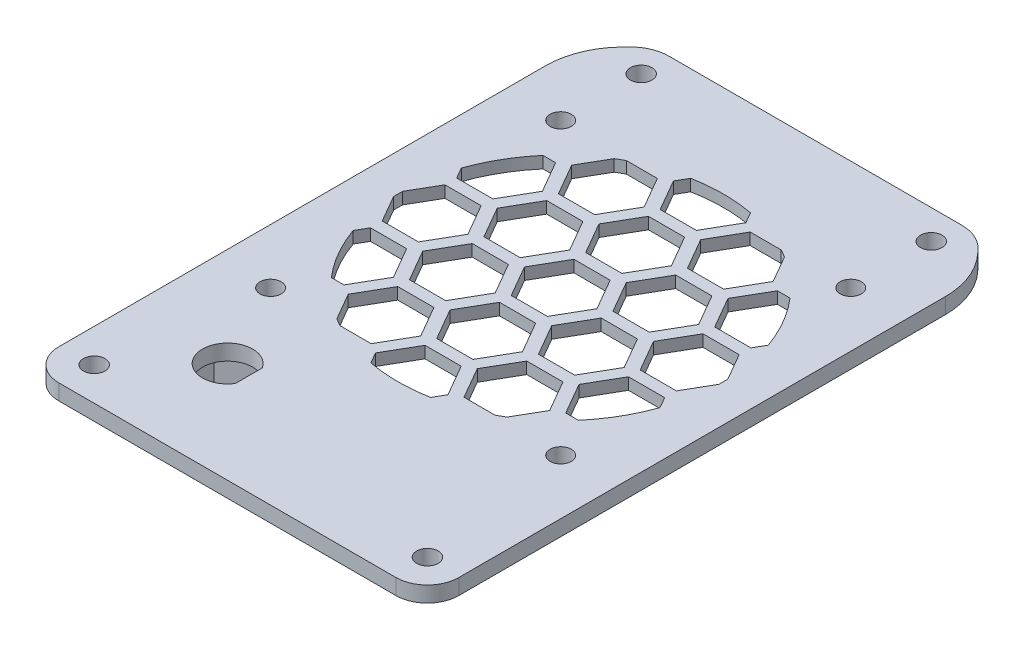
SolidWorks part; units mm, degrees
ref_plane "Front Plane" through (0, 0, 0) normal (0, 0, 1) x (1, 0, 0)
ref_plane "Top Plane" through (0, 0, 0) normal (0, 1, 0) x (1, 0, 0)
ref_plane "Right Plane" through (0, 0, 0) normal (1, 0, 0) x (0, 0, -1)
sketch "Sketch1" plane through (0, -8.5812, 0) normal (0, 1, 0) x (1, 0, 0)
  line L0 (-23.1823, 1.3362) -> (-42.1823, 1.3362)
  line L16 (-54.1823, -73.6638) -> (-11.1823, -73.6638)
  line L17 (-7.1823, -69.6638) -> (-7.1823, -7.6054)
  line L18 (-9.8717, -0.7822) -> (-11.849, 1.3362)
  line L19 (-11.849, 1.3362) -> (-23.1823, 1.3362)
  line L20 (-23.1823, 1.3362) -> (-23.1823, -1.1769)
  line L21 (-23.1823, -1.1769) -> (-10.589, -9.0704)
  line L22 (-9.1823, -11.6123) -> (-9.1823, -59.6638)
  line L23 (-9.1823, -59.6638) -> (-21.1823, -71.6638)
  line L24 (-21.1823, -71.6638) -> (-44.1823, -71.6638)
  line L25 (-44.1823, -71.6638) -> (-56.1823, -59.6638)
  line L26 (-56.1823, -59.6638) -> (-56.1823, -11.6123)
  line L27 (-54.7756, -9.0704) -> (-42.1823, -1.1769)
  line L28 (-42.1823, -1.1769) -> (-42.1823, 1.3362)
  line L29 (-42.1823, 1.3362) -> (-53.5156, 1.3362)
  line L30 (-53.5156, 1.3362) -> (-55.4928, -0.7822)
  line L31 (-58.1823, -7.6054) -> (-58.1823, -69.6638)
  line L32 (-54.1823, -73.6638) -> (-11.1823, -73.6638)
  line L33 (-7.1823, -69.6638) -> (-7.1823, -7.6054)
  line L34 (-9.8717, -0.7822) -> (-11.849, 1.3362)
  line L35 (-11.849, 1.3362) -> (-23.1823, 1.3362)
  line L36 (-23.1823, 1.3362) -> (-23.1823, -1.1769)
  line L37 (-23.1823, -1.1769) -> (-10.589, -9.0704)
  line L38 (-9.1823, -11.6123) -> (-9.1823, -59.6638)
  line L39 (-9.1823, -59.6638) -> (-21.1823, -71.6638)
  line L40 (-21.1823, -71.6638) -> (-44.1823, -71.6638)
  line L41 (-44.1823, -71.6638) -> (-56.1823, -59.6638)
  line L42 (-56.1823, -59.6638) -> (-56.1823, -11.6123)
  line L43 (-54.7756, -9.0704) -> (-42.1823, -1.1769)
  line L44 (-42.1823, -1.1769) -> (-42.1823, 1.3362)
  line L45 (-42.1823, 1.3362) -> (-53.5156, 1.3362)
  line L46 (-53.5156, 1.3362) -> (-55.4928, -0.7822)
  line L47 (-58.1823, -7.6054) -> (-58.1823, -69.6638)
  circle A0 centre (-14.1823, -2.3941) radius 1.375
  circle A1 centre (-51.1823, -2.3941) radius 1.375
  circle A2 centre (-11.4323, -69.4138) radius 1.375
  circle A3 centre (-53.9323, -69.4138) radius 1.375
  arc A6 (-11.1823, -73.6638) -> (-7.1823, -69.6638) centre (-11.1823, -69.6638) ccw
  arc A7 (-7.1823, -7.6054) -> (-9.8717, -0.7822) centre (-17.1823, -7.6054) ccw
  arc A8 (-9.1823, -11.6123) -> (-10.589, -9.0704) centre (-12.1823, -11.6123) ccw
  arc A9 (-54.7756, -9.0704) -> (-56.1823, -11.6123) centre (-53.1823, -11.6123) ccw
  arc A10 (-55.4928, -0.7822) -> (-58.1823, -7.6054) centre (-48.1823, -7.6054) ccw
  arc A11 (-58.1823, -69.6638) -> (-54.1823, -73.6638) centre (-54.1823, -69.6638) ccw
  arc A12 (-11.1823, -73.6638) -> (-7.1823, -69.6638) centre (-11.1823, -69.6638) ccw
  arc A13 (-7.1823, -7.6054) -> (-9.8717, -0.7822) centre (-17.1823, -7.6054) ccw
  arc A14 (-9.1823, -11.6123) -> (-10.589, -9.0704) centre (-12.1823, -11.6123) ccw
  arc A15 (-54.7756, -9.0704) -> (-56.1823, -11.6123) centre (-53.1823, -11.6123) ccw
  arc A16 (-55.4928, -0.7822) -> (-58.1823, -7.6054) centre (-48.1823, -7.6054) ccw
  arc A17 (-58.1823, -69.6638) -> (-54.1823, -73.6638) centre (-54.1823, -69.6638) ccw
  circle M24 centre (-51.1823, -2.3941) radius 2.3
  circle M25 centre (-11.4323, -69.4138) radius 2.3
  circle M26 centre (-53.9323, -69.4138) radius 2.3
  circle M27 centre (-14.1823, -2.3941) radius 2.3
  line M28 (-54.1823, -73.6638) -> (-11.1823, -73.6638)
  arc M29 (-11.1823, -73.6638) -> (-7.1823, -69.6638) centre (-11.1823, -69.6638) ccw
  line M30 (-7.1823, -69.6638) -> (-7.1823, -7.6054)
  arc M31 (-7.1823, -7.6054) -> (-9.8717, -0.7822) centre (-17.1823, -7.6054) ccw
  line M32 (-9.8717, -0.7822) -> (-11.849, 1.3362)
  line M33 (-11.849, 1.3362) -> (-23.1823, 1.3362)
  line M34 (-23.1823, 1.3362) -> (-23.1823, -1.1769)
  line M35 (-23.1823, -1.1769) -> (-10.589, -9.0704)
  arc M36 (-10.589, -9.0704) -> (-9.1823, -11.6123) centre (-12.1823, -11.6123) cw
  line M37 (-9.1823, -11.6123) -> (-9.1823, -59.6638)
  line M38 (-9.1823, -59.6638) -> (-21.1823, -71.6638)
  line M39 (-21.1823, -71.6638) -> (-44.1823, -71.6638)
  line M40 (-44.1823, -71.6638) -> (-56.1823, -59.6638)
  line M41 (-56.1823, -59.6638) -> (-56.1823, -11.6123)
  arc M42 (-56.1823, -11.6123) -> (-54.7756, -9.0704) centre (-53.1823, -11.6123) cw
  line M43 (-54.7756, -9.0704) -> (-42.1823, -1.1769)
  line M44 (-42.1823, -1.1769) -> (-42.1823, 1.3362)
  line M45 (-42.1823, 1.3362) -> (-53.5156, 1.3362)
  line M46 (-53.5156, 1.3362) -> (-55.4928, -0.7822)
  arc M47 (-55.4928, -0.7822) -> (-58.1823, -7.6054) centre (-48.1823, -7.6054) ccw
  line M48 (-58.1823, -7.6054) -> (-58.1823, -69.6638)
  arc M49 (-58.1823, -69.6638) -> (-54.1823, -73.6638) centre (-54.1823, -69.6638) ccw
  dimension "D2" = 2.75
  dimension "D3" = 2.75
  dimension "D4" = 2.75
  dimension "D5" = 2.75
  dimension "D1" = 0
extrude "Boss-Extrude1" add sketch "Sketch1" along normal blind 2 contours M49 M28 M29 M30 M31 M32 M33 M34 M35 M36 M37 M38 M39 M40 M41 M42 M43 M44 M45 M46 M47 M48 M25 M27 M26 M24 | L0 M34 M44 M43 M42 M41 M40 M39 M38 M37 M36 M35 | A0 M27 | A1 M24 | A3 M26 | A2 M25 region at (-32.6823, -8.5812, 35.6933) region at (-17.5156, -8.5812, -0.4292) region at (-53.4172, -8.5812, 2.3941) region at (-13.6672, -8.5812, 69.4138) region at (-56.1672, -8.5812, 69.4138) region at (-16.4172, -8.5812, 2.3941)
fillet "Fillet1" radius 5 2 edges at (-11.849, -7.5812, -1.3362) (-53.5156, -7.5812, -1.3362)
sketch "Sketch2" plane through (0, -6.5812, 0) normal (0, 1, 0) x (1, 0, 0)
  circle A1 centre (-32.6823, -31.1638) radius 20.75
  circle A2 centre (-32.6823, -31.1638) radius 20.75
  dimension "D1" = 0
extrude "Cut-Extrude1" cut sketch "Sketch2" against normal through all
sketch "Sketch3" plane through (0, -8.5812, 0) normal (0, -1, 0) x (1, 0, 0)
  circle A2 centre (-32.6823, 31.1638) radius 21.75
  circle A3 centre (-32.6823, 31.1638) radius 21.75
  dimension "D1" = 1
extrude "Cut-Extrude2" cut sketch "Sketch3" against normal blind 0.5
sketch "Sketch4" plane through (0, -6.5812, 0) normal (0, 1, 0) x (1, 0, 0)
  line L0 (-49.1368, -12.1638) -> (-40.9095, -16.9138) construction
  line L1 (-38.6001, -12.9138) -> (-43.2189, -12.9138)
  line L2 (-43.2189, -12.9138) -> (-45.5283, -16.9138)
  line L3 (-45.5283, -16.9138) -> (-43.2189, -20.9138)
  line L4 (-43.2189, -20.9138) -> (-38.6001, -20.9138)
  line L5 (-38.6001, -20.9138) -> (-36.2907, -16.9138)
  line L6 (-36.2907, -16.9138) -> (-38.6001, -12.9138)
  line L7 (-44.518, -12.1638) -> (-46.8274, -8.1638)
  line L8 (-46.8274, -8.1638) -> (-51.4462, -8.1638)
  line L9 (-51.4462, -8.1638) -> (-53.7556, -12.1638)
  line L10 (-53.7556, -12.1638) -> (-51.4462, -16.1638)
  line L11 (-51.4462, -16.1638) -> (-46.8274, -16.1638)
  line L12 (-46.8274, -16.1638) -> (-44.518, -12.1638)
  line L13 (-22.1456, -12.9138) -> (-26.7644, -12.9138)
  line L14 (-26.7644, -12.9138) -> (-29.0738, -16.9138)
  line L15 (-29.0738, -16.9138) -> (-26.7644, -20.9138)
  line L16 (-26.7644, -20.9138) -> (-22.1456, -20.9138)
  line L17 (-22.1456, -20.9138) -> (-19.8362, -16.9138)
  line L18 (-19.8362, -16.9138) -> (-22.1456, -12.9138)
  line L19 (-28.0635, -12.1638) -> (-30.3729, -8.1638)
  line L20 (-34.9917, -8.1638) -> (-37.3011, -12.1638)
  line L21 (-37.3011, -12.1638) -> (-34.9917, -16.1638)
  line L22 (-34.9917, -16.1638) -> (-30.3729, -16.1638)
  line L23 (-30.3729, -16.1638) -> (-28.0635, -12.1638)
  line L24 (-32.6823, -12.1638) -> (-24.455, -16.9138) construction
  line L25 (-30.3729, -8.1638) -> (-34.9917, -8.1638)
  line L26 (-5.6912, -12.9138) -> (-10.31, -12.9138)
  line L27 (-10.31, -12.9138) -> (-12.6194, -16.9138)
  line L28 (-12.6194, -16.9138) -> (-10.31, -20.9138)
  line L29 (-10.31, -20.9138) -> (-5.6912, -20.9138)
  line L30 (-5.6912, -20.9138) -> (-3.3818, -16.9138)
  line L31 (-3.3818, -16.9138) -> (-5.6912, -12.9138)
  line L32 (-11.609, -12.1638) -> (-13.9184, -8.1638)
  line L33 (-18.5372, -8.1638) -> (-20.8466, -12.1638)
  line L34 (-20.8466, -12.1638) -> (-18.5372, -16.1638)
  line L35 (-18.5372, -16.1638) -> (-13.9184, -16.1638)
  line L36 (-13.9184, -16.1638) -> (-11.609, -12.1638)
  line L37 (-16.2278, -12.1638) -> (-8.0006, -16.9138) construction
  line L38 (-13.9184, -8.1638) -> (-18.5372, -8.1638)
  line L39 (-22.1456, -22.4138) -> (-26.7644, -22.4138)
  line L40 (-26.7644, -22.4138) -> (-29.0738, -26.4138)
  line L41 (-29.0738, -26.4138) -> (-26.7644, -30.4138)
  line L42 (-26.7644, -30.4138) -> (-22.1456, -30.4138)
  line L43 (-22.1456, -30.4138) -> (-19.8362, -26.4138)
  line L44 (-19.8362, -26.4138) -> (-22.1456, -22.4138)
  line L45 (-28.0635, -21.6638) -> (-30.3729, -17.6638)
  line L46 (-34.9917, -17.6638) -> (-37.3011, -21.6638)
  line L47 (-37.3011, -21.6638) -> (-34.9917, -25.6638)
  line L48 (-34.9917, -25.6638) -> (-30.3729, -25.6638)
  line L49 (-30.3729, -25.6638) -> (-28.0635, -21.6638)
  line L50 (-32.6823, -21.6638) -> (-24.455, -26.4138) construction
  line L51 (-30.3729, -17.6638) -> (-34.9917, -17.6638)
  line L52 (-5.6912, -22.4138) -> (-10.31, -22.4138)
  line L53 (-10.31, -22.4138) -> (-12.6194, -26.4138)
  line L54 (-12.6194, -26.4138) -> (-10.31, -30.4138)
  line L55 (-10.31, -30.4138) -> (-5.6912, -30.4138)
  line L56 (-5.6912, -30.4138) -> (-3.3818, -26.4138)
  line L57 (-3.3818, -26.4138) -> (-5.6912, -22.4138)
  line L58 (-11.609, -21.6638) -> (-13.9184, -17.6638)
  line L59 (-18.5372, -17.6638) -> (-20.8466, -21.6638)
  line L60 (-20.8466, -21.6638) -> (-18.5372, -25.6638)
  line L61 (-18.5372, -25.6638) -> (-13.9184, -25.6638)
  line L62 (-13.9184, -25.6638) -> (-11.609, -21.6638)
  line L63 (-16.2278, -21.6638) -> (-8.0006, -26.4138) construction
  line L64 (-13.9184, -17.6638) -> (-18.5372, -17.6638)
  line L65 (-22.1456, -31.9138) -> (-26.7644, -31.9138)
  line L66 (-26.7644, -31.9138) -> (-29.0738, -35.9138)
  line L67 (-29.0738, -35.9138) -> (-26.7644, -39.9138)
  line L68 (-26.7644, -39.9138) -> (-22.1456, -39.9138)
  line L69 (-22.1456, -39.9138) -> (-19.8362, -35.9138)
  line L70 (-19.8362, -35.9138) -> (-22.1456, -31.9138)
  line L71 (-28.0635, -31.1638) -> (-30.3729, -27.1638)
  line L72 (-34.9917, -27.1638) -> (-37.3011, -31.1638)
  line L73 (-37.3011, -31.1638) -> (-34.9917, -35.1638)
  line L74 (-34.9917, -35.1638) -> (-30.3729, -35.1638)
  line L75 (-30.3729, -35.1638) -> (-28.0635, -31.1638)
  line L76 (-32.6823, -31.1638) -> (-24.455, -35.9138) construction
  line L77 (-30.3729, -27.1638) -> (-34.9917, -27.1638)
  line L78 (-5.6912, -31.9138) -> (-10.31, -31.9138)
  line L79 (-10.31, -31.9138) -> (-12.6194, -35.9138)
  line L80 (-12.6194, -35.9138) -> (-10.31, -39.9138)
  line L81 (-10.31, -39.9138) -> (-5.6912, -39.9138)
  line L82 (-5.6912, -39.9138) -> (-3.3818, -35.9138)
  line L83 (-3.3818, -35.9138) -> (-5.6912, -31.9138)
  line L84 (-11.609, -31.1638) -> (-13.9184, -27.1638)
  line L85 (-18.5372, -27.1638) -> (-20.8466, -31.1638)
  line L86 (-20.8466, -31.1638) -> (-18.5372, -35.1638)
  line L87 (-18.5372, -35.1638) -> (-13.9184, -35.1638)
  line L88 (-13.9184, -35.1638) -> (-11.609, -31.1638)
  line L89 (-16.2278, -31.1638) -> (-8.0006, -35.9138) construction
  line L90 (-13.9184, -27.1638) -> (-18.5372, -27.1638)
  line L91 (-22.1456, -41.4138) -> (-26.7644, -41.4138)
  line L92 (-26.7644, -41.4138) -> (-29.0738, -45.4138)
  line L93 (-29.0738, -45.4138) -> (-26.7644, -49.4138)
  line L94 (-26.7644, -49.4138) -> (-22.1456, -49.4138)
  line L95 (-22.1456, -49.4138) -> (-19.8362, -45.4138)
  line L96 (-19.8362, -45.4138) -> (-22.1456, -41.4138)
  line L97 (-28.0635, -40.6638) -> (-30.3729, -36.6638)
  line L98 (-34.9917, -36.6638) -> (-37.3011, -40.6638)
  line L99 (-37.3011, -40.6638) -> (-34.9917, -44.6638)
  line L100 (-34.9917, -44.6638) -> (-30.3729, -44.6638)
  line L101 (-30.3729, -44.6638) -> (-28.0635, -40.6638)
  line L102 (-32.6823, -40.6638) -> (-24.455, -45.4138) construction
  line L103 (-30.3729, -36.6638) -> (-34.9917, -36.6638)
  line L104 (-5.6912, -41.4138) -> (-10.31, -41.4138)
  line L105 (-10.31, -41.4138) -> (-12.6194, -45.4138)
  line L106 (-12.6194, -45.4138) -> (-10.31, -49.4138)
  line L107 (-10.31, -49.4138) -> (-5.6912, -49.4138)
  line L108 (-5.6912, -49.4138) -> (-3.3818, -45.4138)
  line L109 (-3.3818, -45.4138) -> (-5.6912, -41.4138)
  line L110 (-11.609, -40.6638) -> (-13.9184, -36.6638)
  line L111 (-18.5372, -36.6638) -> (-20.8466, -40.6638)
  line L112 (-20.8466, -40.6638) -> (-18.5372, -44.6638)
  line L113 (-18.5372, -44.6638) -> (-13.9184, -44.6638)
  line L114 (-13.9184, -44.6638) -> (-11.609, -40.6638)
  line L115 (-16.2278, -40.6638) -> (-8.0006, -45.4138) construction
  line L116 (-13.9184, -36.6638) -> (-18.5372, -36.6638)
  line L117 (-22.1456, -50.9138) -> (-26.7644, -50.9138)
  line L118 (-26.7644, -50.9138) -> (-29.0738, -54.9138)
  line L119 (-29.0738, -54.9138) -> (-26.7644, -58.9138)
  line L120 (-26.7644, -58.9138) -> (-22.1456, -58.9138)
  line L121 (-22.1456, -58.9138) -> (-19.8362, -54.9138)
  line L122 (-19.8362, -54.9138) -> (-22.1456, -50.9138)
  line L123 (-28.0635, -50.1638) -> (-30.3729, -46.1638)
  line L124 (-34.9917, -46.1638) -> (-37.3011, -50.1638)
  line L125 (-37.3011, -50.1638) -> (-34.9917, -54.1638)
  line L126 (-34.9917, -54.1638) -> (-30.3729, -54.1638)
  line L127 (-30.3729, -54.1638) -> (-28.0635, -50.1638)
  line L128 (-32.6823, -50.1638) -> (-24.455, -54.9138) construction
  line L129 (-30.3729, -46.1638) -> (-34.9917, -46.1638)
  line L130 (-5.6912, -50.9138) -> (-10.31, -50.9138)
  line L131 (-10.31, -50.9138) -> (-12.6194, -54.9138)
  line L132 (-12.6194, -54.9138) -> (-10.31, -58.9138)
  line L133 (-10.31, -58.9138) -> (-5.6912, -58.9138)
  line L134 (-5.6912, -58.9138) -> (-3.3818, -54.9138)
  line L135 (-3.3818, -54.9138) -> (-5.6912, -50.9138)
  line L136 (-11.609, -50.1638) -> (-13.9184, -46.1638)
  line L137 (-18.5372, -46.1638) -> (-20.8466, -50.1638)
  line L138 (-20.8466, -50.1638) -> (-18.5372, -54.1638)
  line L139 (-18.5372, -54.1638) -> (-13.9184, -54.1638)
  line L140 (-13.9184, -54.1638) -> (-11.609, -50.1638)
  line L141 (-16.2278, -50.1638) -> (-8.0006, -54.9138) construction
  line L142 (-13.9184, -46.1638) -> (-18.5372, -46.1638)
  line L143 (-38.6001, -22.4138) -> (-43.2189, -22.4138)
  line L144 (-43.2189, -22.4138) -> (-45.5283, -26.4138)
  line L145 (-45.5283, -26.4138) -> (-43.2189, -30.4138)
  line L146 (-43.2189, -30.4138) -> (-38.6001, -30.4138)
  line L147 (-38.6001, -30.4138) -> (-36.2907, -26.4138)
  line L148 (-36.2907, -26.4138) -> (-38.6001, -22.4138)
  line L149 (-44.518, -21.6638) -> (-46.8274, -17.6638)
  line L150 (-51.4462, -17.6638) -> (-53.7556, -21.6638)
  line L151 (-53.7556, -21.6638) -> (-51.4462, -25.6638)
  line L152 (-51.4462, -25.6638) -> (-46.8274, -25.6638)
  line L153 (-46.8274, -25.6638) -> (-44.518, -21.6638)
  line L154 (-49.1368, -21.6638) -> (-40.9095, -26.4138) construction
  line L155 (-46.8274, -17.6638) -> (-51.4462, -17.6638)
  line L156 (-38.6001, -31.9138) -> (-43.2189, -31.9138)
  line L157 (-43.2189, -31.9138) -> (-45.5283, -35.9138)
  line L158 (-45.5283, -35.9138) -> (-43.2189, -39.9138)
  line L159 (-43.2189, -39.9138) -> (-38.6001, -39.9138)
  line L160 (-38.6001, -39.9138) -> (-36.2907, -35.9138)
  line L161 (-36.2907, -35.9138) -> (-38.6001, -31.9138)
  line L162 (-44.518, -31.1638) -> (-46.8274, -27.1638)
  line L163 (-51.4462, -27.1638) -> (-53.7556, -31.1638)
  line L164 (-53.7556, -31.1638) -> (-51.4462, -35.1638)
  line L165 (-51.4462, -35.1638) -> (-46.8274, -35.1638)
  line L166 (-46.8274, -35.1638) -> (-44.518, -31.1638)
  line L167 (-49.1368, -31.1638) -> (-40.9095, -35.9138) construction
  line L168 (-46.8274, -27.1638) -> (-51.4462, -27.1638)
  line L169 (-38.6001, -41.4138) -> (-43.2189, -41.4138)
  line L170 (-43.2189, -41.4138) -> (-45.5283, -45.4138)
  line L171 (-45.5283, -45.4138) -> (-43.2189, -49.4138)
  line L172 (-43.2189, -49.4138) -> (-38.6001, -49.4138)
  line L173 (-38.6001, -49.4138) -> (-36.2907, -45.4138)
  line L174 (-36.2907, -45.4138) -> (-38.6001, -41.4138)
  line L175 (-44.518, -40.6638) -> (-46.8274, -36.6638)
  line L176 (-51.4462, -36.6638) -> (-53.7556, -40.6638)
  line L177 (-53.7556, -40.6638) -> (-51.4462, -44.6638)
  line L178 (-51.4462, -44.6638) -> (-46.8274, -44.6638)
  line L179 (-46.8274, -44.6638) -> (-44.518, -40.6638)
  line L180 (-49.1368, -40.6638) -> (-40.9095, -45.4138) construction
  line L181 (-46.8274, -36.6638) -> (-51.4462, -36.6638)
  line L182 (-38.6001, -50.9138) -> (-43.2189, -50.9138)
  line L183 (-43.2189, -50.9138) -> (-45.5283, -54.9138)
  line L184 (-45.5283, -54.9138) -> (-43.2189, -58.9138)
  line L185 (-43.2189, -58.9138) -> (-38.6001, -58.9138)
  line L186 (-38.6001, -58.9138) -> (-36.2907, -54.9138)
  line L187 (-36.2907, -54.9138) -> (-38.6001, -50.9138)
  line L188 (-44.518, -50.1638) -> (-46.8274, -46.1638)
  line L189 (-51.4462, -46.1638) -> (-53.7556, -50.1638)
  line L190 (-53.7556, -50.1638) -> (-51.4462, -54.1638)
  line L191 (-51.4462, -54.1638) -> (-46.8274, -54.1638)
  line L192 (-46.8274, -54.1638) -> (-44.518, -50.1638)
  line L193 (-49.1368, -50.1638) -> (-40.9095, -54.9138) construction
  line L194 (-46.8274, -46.1638) -> (-51.4462, -46.1638)
  circle A0 centre (-40.9095, -16.9138) radius 4 construction
  circle A1 centre (-49.1368, -12.1638) radius 4 construction
  circle A2 centre (-24.455, -16.9138) radius 4 construction
  circle A3 centre (-32.6823, -12.1638) radius 4 construction
  circle A4 centre (-8.0006, -16.9138) radius 4 construction
  circle A5 centre (-16.2278, -12.1638) radius 4 construction
  circle A6 centre (-24.455, -26.4138) radius 4 construction
  circle A7 centre (-32.6823, -21.6638) radius 4 construction
  circle A8 centre (-8.0006, -26.4138) radius 4 construction
  circle A9 centre (-16.2278, -21.6638) radius 4 construction
  circle A10 centre (-24.455, -35.9138) radius 4 construction
  circle A11 centre (-32.6823, -31.1638) radius 4 construction
  circle A12 centre (-8.0006, -35.9138) radius 4 construction
  circle A13 centre (-16.2278, -31.1638) radius 4 construction
  circle A14 centre (-24.455, -45.4138) radius 4 construction
  circle A15 centre (-32.6823, -40.6638) radius 4 construction
  circle A16 centre (-8.0006, -45.4138) radius 4 construction
  circle A17 centre (-16.2278, -40.6638) radius 4 construction
  circle A18 centre (-24.455, -54.9138) radius 4 construction
  circle A19 centre (-32.6823, -50.1638) radius 4 construction
  circle A20 centre (-8.0006, -54.9138) radius 4 construction
  circle A21 centre (-16.2278, -50.1638) radius 4 construction
  circle A22 centre (-40.9095, -26.4138) radius 4 construction
  circle A23 centre (-49.1368, -21.6638) radius 4 construction
  circle A24 centre (-40.9095, -35.9138) radius 4 construction
  circle A25 centre (-49.1368, -31.1638) radius 4 construction
  circle A26 centre (-40.9095, -45.4138) radius 4 construction
  circle A27 centre (-49.1368, -40.6638) radius 4 construction
  circle A28 centre (-40.9095, -54.9138) radius 4 construction
  circle A29 centre (-49.1368, -50.1638) radius 4 construction
  circle A32 centre (-32.6823, -31.1638) radius 20.75
  point P21 (-40.9095, -20.9138)
  point P243 (-32.6823, -31.1638)
  circle M226 centre (-32.6823, -31.1638) radius 20.75
  dimension "D1" = 8
  dimension "D2" = 1.5
  dimension "D5" = 1.5
  dimension "D6" = 1.5
  dimension "D3" = 3
  dimension "D4" = 5
extrude "Boss-Extrude2" add sketch "Sketch4" against normal up to surface (1.5 mm away) contours L194 L188 L171 L170 L169 L174 L173 L172 L182 L187 L125 L124 L129 L123 L127 L118 L117 L94 L93 L92 L91 L96 L95 L137 L142 L113 L112 L111 L116 L110 L80 L79 L88 L87 L86 L85 L90 L84 L54 L53 M226 | L11 L12 M226 | L188 L194 M226 | L142 L137 M226 | L34 L35 M226 | L187 L182 M226 | L117 L118 M226 | L79 L80 M226 | L53 L54 M226 region at (-40.5783, -6.5812, 12.332) region at (-46.817, -6.5812, 16.0338) region at (-18.5475, -6.5812, 16.0338) region at (-12.5119, -6.5812, 26.4878) region at (-46.817, -6.5812, 46.2938) region at (-12.5119, -6.5812, 35.8398) region at (-38.7179, -6.5812, 50.9699) region at (-18.5475, -6.5812, 46.2938) region at (-26.6467, -6.5812, 50.9699) up to face at (-32.6823, -8.0812, 9.4138)
sketch "Sketch8" plane through (0, -6.5812, 0) normal (0, 1, 0) x (1, 0, 0)
  line L0 (-42.8661, -59.045) -> (-42.8661, -62.4801)
  circle A0 centre (-45.5661, -60.7626) radius 3.2
  dimension "D1" = 6.4
  dimension "D2" = 2.7
extrude "Cut-Extrude3" cut sketch "Sketch8" against normal through all contours L0 A0 region at (-45.675, -6.5812, 60.7626)
sketch "Sketch9" plane through (0, -8.5812, 0) normal (0, -1, 0) x (1, 0, 0)
  line L0 (-42.8661, 59.045) -> (-42.8661, 62.4801) construction
  line L1 (-41.3911, 58.3522) -> (-41.3911, 63.173)
  line L2 (-41.3911, 63.173) -> (-45.5661, 65.5835)
  line L3 (-45.5661, 65.5835) -> (-49.7411, 63.173)
  line L4 (-49.7411, 63.173) -> (-49.7411, 58.3522)
  line L5 (-49.7411, 58.3522) -> (-45.5661, 55.9417)
  line L6 (-45.5661, 55.9417) -> (-41.3911, 58.3522)
  circle A0 centre (-45.5661, 60.7626) radius 4.175 construction
  circle A1 centre (-45.5661, 60.7626) radius 6
  dimension "D2" = 12
  dimension "D1" = 8.35
extrude "Boss-Extrude3" add sketch "Sketch9" along normal blind 5 contours A1 L6 L5 L4 L3 L2 L1 region at (-51.3964, -8.5812, 60.7626)
sketch "Sketch10" plane through (0, -6.5812, 0) normal (0, 1, 0) x (1, 0, 0)
  circle A0 centre (-14.1823, -49.6638) radius 1.5 construction
  circle A1 centre (-14.1823, -12.6638) radius 1.5 construction
  circle A2 centre (-51.1823, -12.6638) radius 1.5 construction
  circle A3 centre (-51.1823, -49.6638) radius 1.5 construction
  circle A4 centre (-14.1823, -49.6638) radius 1.5 construction
  circle A5 centre (-14.1823, -12.6638) radius 1.5 construction
  circle A6 centre (-51.1823, -12.6638) radius 1.5 construction
  circle A7 centre (-51.1823, -49.6638) radius 1.5 construction
  circle A8 centre (-14.1823, -49.6638) radius 1.35
  circle A9 centre (-51.1823, -49.6638) radius 1.35
  circle A10 centre (-51.1823, -12.6638) radius 1.35
  circle A11 centre (-14.1823, -12.6638) radius 1.35
  dimension "D1" = 2.7
  dimension "D2" = 2.7
  dimension "D3" = 2.7
  dimension "D4" = 2.7
extrude "Cut-Extrude4" cut sketch "Sketch10" against normal through all
